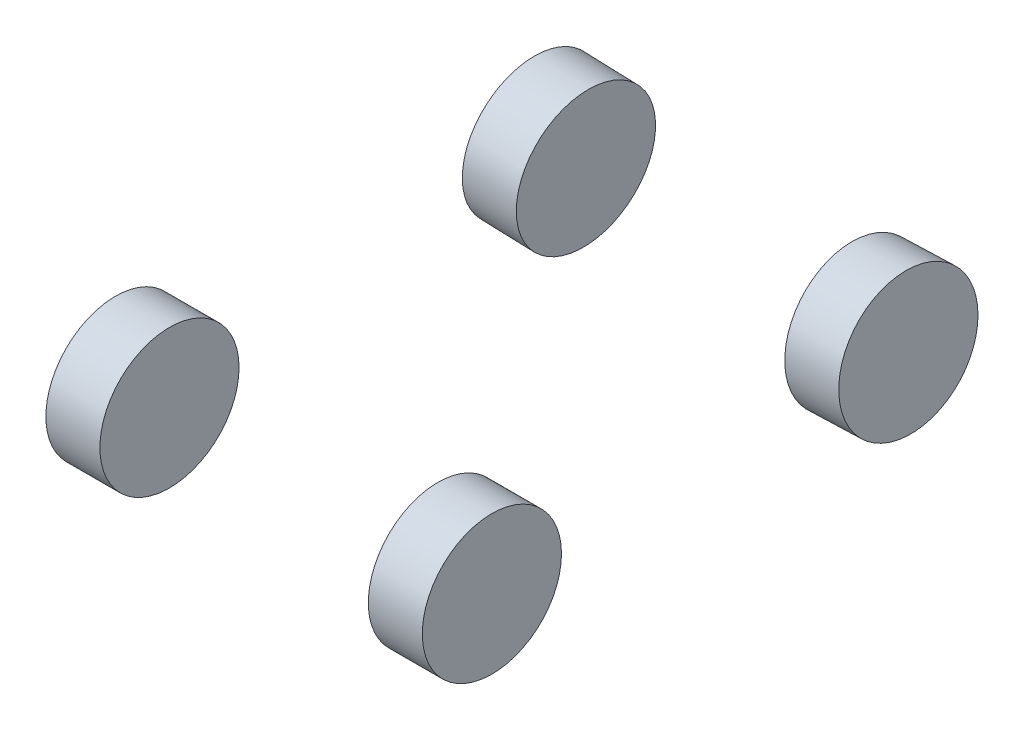
SolidWorks part; units mm, degrees
ref_plane "Front Plane" through (0, 0, 0) normal (0, 0, 1) x (1, 0, 0)
ref_plane "Top Plane" through (0, 0, 0) normal (0, 1, 0) x (1, 0, 0)
ref_plane "Right Plane" through (0, 0, 0) normal (1, 0, 0) x (0, 0, -1)
sketch3d "3DSketch1"
  line L0 (-519.3255, 235, 2080) -> (-681.2452, 235, 2080) construction
  line L1 (-681.2452, 235, 2080) -> (-684.2452, 235, 2080) construction
  line L2 (-519.3255, 235, 2080) -> (-412.1048, 235, 2080) construction
  line L3 (-600, 235, 2080) -> (-600, 486.5176, 2141.8052) construction
  line L4 (-600, 235, 2080) -> (-600, 173.1948, 2331.5176) construction
  line L5 (-600, 235, 2080) -> (-600, 235, 2339) construction
  arc A0 (-681.2452, 468.1652, 2050.6914) -> (-681.2452, 1.8348, 2109.3086) centre (-681.2452, 235, 2080) ccw construction
  arc A1 (-681.2452, 468.1652, 2050.6914) -> (-681.2452, 1.8348, 2109.3086) centre (-681.2452, 235, 2080) ccw construction
  arc A2 (-519.3255, 468.1652, 2050.6914) -> (-519.3255, 1.8348, 2109.3086) centre (-519.3255, 235, 2080) ccw construction
  arc A3 (-519.3255, 468.1652, 2050.6914) -> (-519.3255, 1.8348, 2109.3086) centre (-519.3255, 235, 2080) ccw construction
  arc A4 (-681.2452, 1.8348, 2109.3086) -> (-681.2452, 468.1652, 2050.6914) centre (-681.2452, 235, 2080) ccw construction
  arc A5 (-681.2452, 1.8348, 2109.3086) -> (-681.2452, 468.1652, 2050.6914) centre (-681.2452, 235, 2080) ccw construction
  arc A6 (-519.3255, 1.8348, 2109.3086) -> (-519.3255, 468.1652, 2050.6914) centre (-519.3255, 235, 2080) ccw construction
  arc A7 (-519.3255, 1.8348, 2109.3086) -> (-519.3255, 468.1652, 2050.6914) centre (-519.3255, 235, 2080) ccw construction
  circle A10 centre (-600, 235, 2080) radius 259
  point P3 (-916.2452, 235, 2080)
  point P4 (-916.2452, 235, 2080)
  point P8 (-754.3255, 235, 2080)
  point P9 (-754.3255, 235, 2080)
  point P13 (-916.2452, 235, 2080)
  point P14 (-916.2452, 235, 2080)
  point P16 (-754.3255, 235, 2080)
  point P17 (-754.3255, 235, 2080)
  point P22 (-341, 235, 2080)
  dimension "D2" = 518
  dimension "D1" = 3
sketch3d "3DSketch2"
  line L0 (-519.1248, 232.1758, 530) -> (-680.9459, 237.8267, 530) construction
  line L1 (-600.0354, 235.0012, 530) -> (-600.0354, 235.0012, 789) construction
  line L2 (-600.0354, 235.0012, 530) -> (-609.0743, -23.841, 530) construction
  arc A0 (-672.8078, 470.8721, 500.8691) -> (-689.084, 4.7813, 559.1309) centre (-680.9459, 237.8267, 530) ccw construction
  arc A1 (-689.084, 4.7813, 559.1309) -> (-672.8078, 470.8721, 500.8691) centre (-680.9459, 237.8267, 530) ccw construction
  arc A2 (-527.2629, -0.8696, 559.1309) -> (-510.9867, 465.2212, 500.8691) centre (-519.1248, 232.1758, 530) ccw construction
  arc A3 (-510.9867, 465.2212, 500.8691) -> (-527.2629, -0.8696, 559.1309) centre (-519.1248, 232.1758, 530) ccw construction
  arc A4 (-672.8078, 470.8721, 500.8691) -> (-689.084, 4.7813, 559.1309) centre (-680.9459, 237.8267, 530) ccw construction
  arc A5 (-689.084, 4.7813, 559.1309) -> (-672.8078, 470.8721, 500.8691) centre (-680.9459, 237.8267, 530) ccw construction
  arc A6 (-527.2629, -0.8696, 559.1309) -> (-510.9867, 465.2212, 500.8691) centre (-519.1248, 232.1758, 530) ccw construction
  arc A7 (-510.9867, 465.2212, 500.8691) -> (-527.2629, -0.8696, 559.1309) centre (-519.1248, 232.1758, 530) ccw construction
  circle A10 centre (-600.0354, 235.0012, 530) radius 259
  point P3 (-915.8027, 246.0281, 530)
  point P5 (-915.8027, 246.0281, 530)
  point P6 (-915.8027, 246.0281, 530)
  point P7 (-915.8027, 246.0281, 530)
  point P11 (-753.9817, 240.3772, 530)
  point P13 (-753.9817, 240.3772, 530)
  point P14 (-753.9817, 240.3772, 530)
  point P15 (-753.9817, 240.3772, 530)
  point P16 (-599.7502, 234.9913, 530)
  point P19 (-341.1931, 225.9623, 530)
  point P20 (-600.0354, 235.0012, 789)
  point P22 (-609.0743, -23.841, 530)
  dimension "D1" = 518
ref_plane "Plane1" through (-526.5904, 18.3889, 0) normal (-0.9994, 0.0349, 0) x (0, 0, 1)
extrude "Boss-Extrude2" add sketch "3DSketch2" along direction (-0.9994, 0.0349, 0) on the side of the normal blind 100.5 and the other way blind 100.5 separate body
ref_plane "Plane2" through (-519.3255, 0, 0) normal (-1, 0, 0) x (0, 0, 1)
extrude "Boss-Extrude3" add sketch "3DSketch1" along direction (-1, 0, 0) on the side of the normal blind 100.5 and the other way blind 100.5 separate body
mirror "Mirror1" about plane through (0, 0, 0) normal (1, 0, 0) of bodies 102 103
